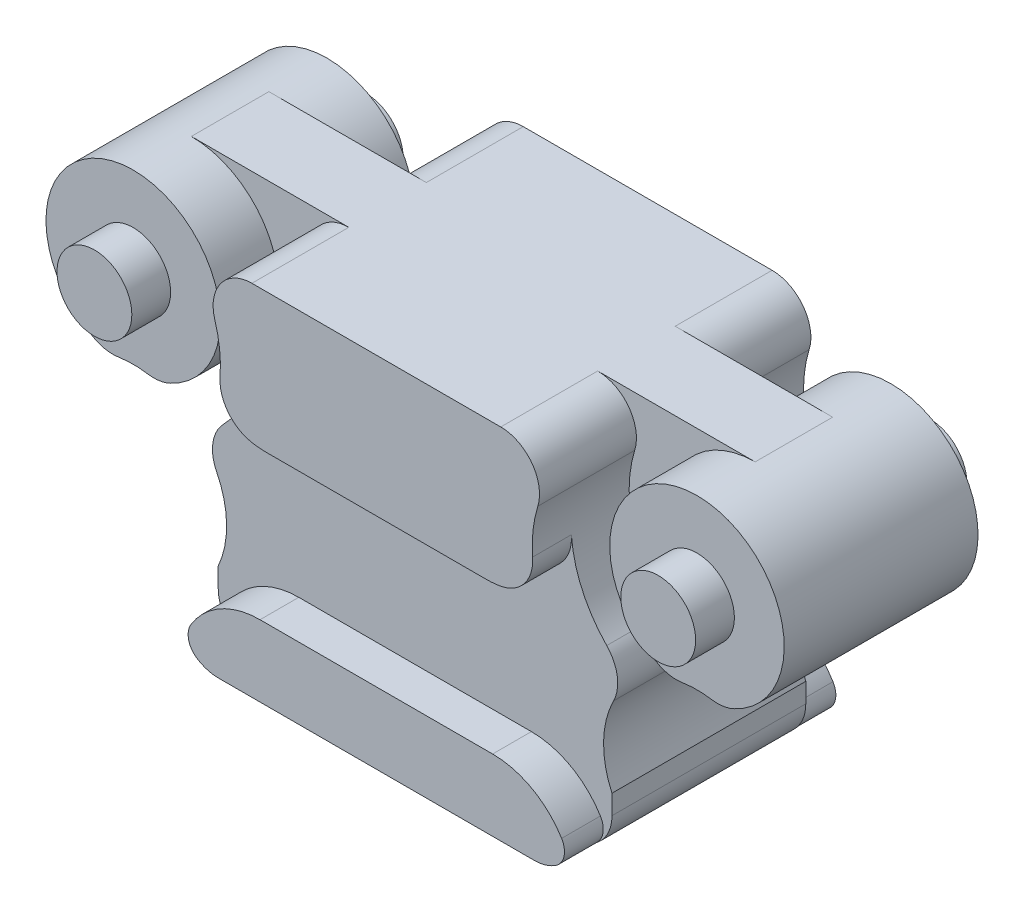
SolidWorks part; units mm, degrees
material "ABS"
ref_plane "Front Plane" through (0, 0, 0) normal (0, 0, 1) x (1, 0, 0)
ref_plane "Top Plane" through (0, 0, 0) normal (0, 1, 0) x (1, 0, 0)
ref_plane "Right Plane" through (0, 0, 0) normal (1, 0, 0) x (0, 0, -1)
sketch "Sketch1" plane through (0, 0, 0) normal (0, 0, 1) x (1, 0, 0)
  line L0 (5.5562, 0) -> (35.7188, 0)
  line L1 (0, 5.5562) -> (41.275, 5.5562)
  line L2 (0, 5.5562) -> (0, -5.5562) construction
  line L3 (0, -5.5562) -> (41.275, -5.5562) construction
  line L4 (41.275, 5.5562) -> (41.275, -5.5562) construction
  line L5 (0, 5.5562) -> (41.275, 5.5562) construction
  line L9 (0, 0) -> (9.0934, 0.7956) construction
  line L10 (41.275, 9.1281) -> (41.275, 0) construction
  line L11 (32.1816, 0.7956) -> (30.4025, 0.9512) construction
  line L12 (32.1816, 0.7956) -> (41.275, 0) construction
  line L13 (30.4025, 0.9512) -> (28.6233, 1.1069) construction
  circle A0 centre (0, 0) radius 5.5562 construction
  circle A1 centre (41.275, 0) radius 5.5562 construction
  arc A2 (0, 5.5562) -> (0, -5.5562) centre (0, 0) ccw
  arc A3 (41.275, -5.5562) -> (41.275, 5.5562) centre (41.275, 0) ccw
  circle A4 centre (0, 0) radius 1.7859
  circle A5 centre (41.275, 0) radius 1.7859
  arc A6 (0, -5.5562) -> (5.5562, 0) centre (0, 0) ccw
  arc A7 (35.7188, 0) -> (41.275, -5.5562) centre (41.275, 0) ccw
  circle A16 centre (41.275, -9.1281) radius 1.7859
  circle A20 centre (41.275, -9.1281) radius 3.5719
  circle A21 centre (32.1816, 0.7956) radius 1.7859
  circle A22 centre (32.1816, 0.7956) radius 3.5719 construction
  circle A23 centre (41.275, 0) radius 9.1281 construction
  circle A25 centre (0, 0) radius 9.1281 construction
  circle A40 centre (32.1816, 7.9393) radius 1.7859
  circle A41 centre (32.1816, 7.9393) radius 3.5719
  circle A42 centre (0, -9.1281) radius 3.5719
  circle A46 centre (9.0934, 0.7956) radius 1.7859
  circle A47 centre (9.0934, 7.9393) radius 1.7859
  circle A48 centre (9.0934, 7.9393) radius 3.5719
  circle A49 centre (9.0934, 0.7956) radius 3.5719 construction
  circle A50 centre (0, -9.1281) radius 1.7859
  arc A51 (0, -7.3422) -> (7.3142, 0.6399) centre (0, 0) ccw
  arc A52 (0, -10.9141) -> (10.8725, 0.9512) centre (0, 0) ccw
  arc A53 (0, -12.7) -> (12.6517, 1.1069) centre (0, 0) ccw
  arc A54 (28.6233, 1.1069) -> (41.275, -12.7) centre (41.275, 0) ccw
  arc A55 (30.4025, 0.9512) -> (41.275, -10.9141) centre (41.275, 0) ccw
  arc A56 (33.9608, 0.6399) -> (41.275, -7.3422) centre (41.275, 0) ccw
  dimension "D1" = 41.275
  dimension "D2" = 11.1125
  dimension "D3" = 3.5719
  dimension "D5" = 95
  dimension "D6" = 7.1438
  dimension "D7" = 3.5719
  dimension "D4" = 95
sketch "Sketch2" plane through (0, 0, 0) normal (0, 0, 1) x (1, 0, 0)
  line L0 (9.0934, 11.5112) -> (32.1816, 11.5112)
  line L1 (12.5755, 0) -> (28.6995, 0)
  line L2 (5.5562, 0) -> (35.7188, 0) construction
  line L3 (12.5755, 0) -> (12.5755, -3.175)
  line L4 (12.5755, -3.175) -> (28.6995, -3.175)
  line L5 (28.6995, -3.175) -> (28.6995, 0)
  circle A0 centre (32.1816, 0.7956) radius 3.5719
  circle A1 centre (9.0934, 0.7956) radius 3.5719
  circle A2 centre (9.0934, 7.9393) radius 3.5719
  circle A3 centre (32.1816, 7.9393) radius 3.5719
  circle A4 centre (9.0934, 7.9393) radius 3.5719 construction
  circle A5 centre (32.1816, 0.7956) radius 3.5719 construction
  circle A6 centre (9.0934, 0.7956) radius 3.5719 construction
  circle A7 centre (9.0934, 7.9393) radius 1.5319
  circle A8 centre (32.1816, 7.9393) radius 1.5319
  circle A9 centre (9.0934, 0.7956) radius 3.8259
  circle A10 centre (32.1816, 0.7956) radius 3.8259
  dimension "D2" = 3.0639
  dimension "D3" = 0.254
  dimension "D1" = 3.175
extrude "Boss-Extrude1" add sketch "Sketch2" along normal blind 7.9375 contours A3 L0 A2 A1 L1 A0 | A2 A7 | A3 A8 | L4 L5 L1 L3 region at (20.6375, 5.8629, 0) region at (11.5483, 10.3942, 0) region at (34.6365, 10.3942, 0) region at (20.6375, -1.5934, 0)
extrude "Boss-Extrude2" add sketch "Sketch2<3>" along normal blind 9.525 and the other way blind 1.5875 contours A7 | A8 region at (9.0934, 7.9393, 0)
sketch "Sketch2<3>" plane through (0, 0, 0) normal (0, 0, 1) x (1, 0, 0) same geometry as "Sketch2"
fillet "Fillet1" radius 1.5875 2 edges at (28.6995, -3.175, 3.9688) (12.5755, -3.175, 3.9688)
sketch "Sketch3" plane through (0, -3.175, 0) normal (0, -1, 0) x (-1, 0, 0)
  line L0 (-14.163, -3.9688) -> (-27.112, -3.9688) construction
  line L1 (-14.163, -7.9375) -> (-27.112, -7.9375) construction
  line L2 (-14.163, -7.9375) -> (-14.163, 0) construction
  line L3 (-14.163, 0) -> (-27.112, 0) construction
  line L4 (-27.112, -7.9375) -> (-27.112, 0) construction
  line L6 (-15.7505, -1.5875) -> (-17.338, -1.5875)
  line L7 (-15.7505, -1.5875) -> (-15.7505, -6.35)
  line L8 (-15.7505, -6.35) -> (-17.338, -6.35)
  line L9 (-17.338, -1.5875) -> (-17.338, -6.35)
  line L10 (-15.7505, -1.5875) -> (-17.338, -6.35) construction
  line L11 (-15.7505, -6.35) -> (-17.338, -1.5875) construction
  line L12 (-19.8437, -1.5875) -> (-21.4312, -1.5875)
  line L13 (-19.8437, -1.5875) -> (-19.8437, -6.35)
  line L14 (-19.8437, -6.35) -> (-21.4312, -6.35)
  line L15 (-21.4312, -1.5875) -> (-21.4312, -6.35)
  line L16 (-19.8437, -1.5875) -> (-21.4312, -6.35) construction
  line L17 (-19.8437, -6.35) -> (-21.4312, -1.5875) construction
  line L18 (-23.937, -1.5875) -> (-25.5245, -1.5875)
  line L19 (-23.937, -1.5875) -> (-23.937, -6.35)
  line L20 (-23.937, -6.35) -> (-25.5245, -6.35)
  line L21 (-25.5245, -1.5875) -> (-25.5245, -6.35)
  line L22 (-23.937, -1.5875) -> (-25.5245, -6.35) construction
  line L23 (-23.937, -6.35) -> (-25.5245, -1.5875) construction
  point P8 (-16.5443, -3.9688)
  point P13 (-20.6375, -3.9688)
  point P18 (-24.7307, -3.9688)
  dimension "D1" = 1.5875
  dimension "D2" = 1.5875
  dimension "D3" = 1.5875
  dimension "D4" = 4.7625
extrude "Cut-Extrude1" cut sketch "Sketch3" against normal blind 3.175
sketch "Sketch5" plane through (0, 0, 7.9375) normal (0, 0, 1) x (1, 0, 0)
  line L0 (5.5216, 7.9125) -> (35.7534, 7.9125) construction
  line L1 (9.0934, 11.5112) -> (32.1816, 11.5112) construction
  line L2 (5.5216, 7.9125) -> (11.7547, 11.5112) construction
  arc A0 (9.0934, 11.5112) -> (8.1331, 4.499) centre (9.0934, 7.9393) ccw construction
  arc A1 (33.1419, 4.499) -> (32.1816, 11.5112) centre (32.1816, 7.9393) ccw construction
  dimension "D1" = 3.5987
  dimension "D2" = 30
sketch3d "3DSketch1"
  line L2 (9.0934, 11.5112, 0) -> (32.1816, 11.5112, 0) construction
  line L3 (11.7547, 11.5112, 7.9375) -> (11.7547, 11.5112, 0) construction
sketch3d "3DSketch4"
  line L0 (11.7547, 11.5112, 7.9375) -> (11.7547, 11.5112, 0) construction
  line L1 (5.5216, 7.9125, 7.9375) -> (11.7547, 11.5112, 7.9375) construction
sketch3d "3DSketch6"
sketch "Sketch7" plane through (-2.0458, 3.5435, 0) normal (0.5, -0.866, 0) x (-0.866, -0.5, 0)
  line L0 (-8.7381, -7.9375) -> (-8.7381, 0) construction
  line L1 (-8.2729, 0) -> (-13.6307, 0) construction
ref_plane "Plane2" through (35.7535, 0, 0) normal (1, 0, 0) x (0, 0, -1)
sketch "Sketch8" plane through (7.5674, 4.3691, 0) normal (0.866, 0.5, 0) x (0, 0, -1)
  line L0 (-7.9375, 4.0916) -> (0, 4.0916) construction
  line L2 (-4.7816, 3.2788) -> (-3.156, 3.2788)
  line L3 (-4.7816, 3.2788) -> (-4.7816, 4.9044)
  line L4 (-4.7816, 4.9044) -> (-3.156, 4.9044)
  line L5 (-3.156, 3.2788) -> (-3.156, 4.9044)
  line L6 (-4.7816, 3.2788) -> (-3.156, 4.9044) construction
  line L7 (-4.7816, 4.9044) -> (-3.156, 3.2788) construction
  circle A0 centre (-3.9688, 4.0916) radius 0.8128 construction
  point P4 (-3.9688, 4.0916)
  dimension "D1" = 1.6256
extrude "Cut-Extrude2" [suppressed] cut sketch "Sketch8" against normal through all both and the other way through all
sketch "Sketch9" plane through (35.7535, 0, 0) normal (1, 0, 0) x (0, 0, -1)
  line L0 (-7.9375, 7.9393) -> (0, 7.9393) construction
  line L1 (-7.9375, 9.4713) -> (-7.9375, 6.4074) construction
  line L2 (0, 6.4074) -> (0, 9.4713) construction
  line L4 (-4.3751, 7.5329) -> (-3.5624, 7.5329)
  line L5 (-4.3751, 7.5329) -> (-4.3751, 8.3457)
  line L6 (-4.3751, 8.3457) -> (-3.5624, 8.3457)
  line L7 (-3.5624, 7.5329) -> (-3.5624, 8.3457)
  line L8 (-4.3751, 7.5329) -> (-3.5624, 8.3457) construction
  line L9 (-4.3751, 8.3457) -> (-3.5624, 7.5329) construction
  circle A0 centre (-3.9688, 7.9393) radius 0.4064 construction
  dimension "D1" = 0.8128
extrude "Cut-Extrude3" [suppressed] cut sketch "Sketch9" against normal blind 0.8928
sketch "Sketch10" plane through (0, 0, 7.9375) normal (0, 0, 1) x (1, 0, 0)
  line L0 (9.0934, 11.5112) -> (12.8164, 11.5112)
  line L1 (9.0934, 11.5112) -> (32.1816, 11.5112) construction
  line L2 (32.1816, 11.5112) -> (28.4586, 11.5112)
  circle A0 centre (9.0934, 7.9393) radius 3.5719
  circle A1 centre (9.0934, 7.9393) radius 5.1594
  circle A2 centre (32.1816, 7.9393) radius 3.5719
  circle A3 centre (32.1816, 7.9393) radius 5.1594
  arc A4 (33.1419, 4.499) -> (32.1816, 11.5112) centre (32.1816, 7.9393) ccw construction
  arc A5 (33.1419, 4.499) -> (28.6995, -0.7893) centre (32.1816, 0.7956) ccw construction
  arc A7 (32.1816, 4.3674) -> (29.7343, 3.3973) centre (32.1816, 0.7956) ccw
  arc A8 (11.5407, 3.3973) -> (9.0934, 4.3674) centre (9.0934, 0.7956) ccw
  circle A9 centre (32.1816, 7.9393) radius 1.5319 construction
  arc A10 (12.5755, -0.7893) -> (8.1331, 4.499) centre (9.0934, 0.7956) ccw construction
  line M9 (32.1816, 11.5112) -> (9.0934, 11.5112)
  dimension "D1" = 1.5875
  dimension "D2" = 1.5875
  dimension "D3" = 0.254
  dimension "D4" = 0.254
extrude "Cut-Extrude4" cut sketch "Sketch10" against normal blind 2.3812 contours A1 A0 M9 | A3 A2 M9 region at (10.9549, 11.415, 7.9375) region at (30.3201, 11.415, 7.9375)
extrude "Cut-Extrude5" cut sketch "Sketch10<3>" against normal blind 2.3812 from offset 5.5562 contours A1 A0 M9 | A3 A2 M9 region at (10.9549, 11.415, 7.9375) region at (30.3201, 11.415, 7.9375) offset against normal yes
sketch "Sketch10<3>" plane through (0, 0, 7.9375) normal (0, 0, 1) x (1, 0, 0) same geometry as "Sketch10"
fillet "Fillet2" radius 1.5875 8 edges at (28.4586, 11.5112, 1.1906) (28.4586, 11.5112, 6.7469) (12.8164, 11.5112, 6.7469) (12.8164, 11.5112, 1.1906) (11.7705, 3.5288, 1.1906) (29.5045, 3.5288, 1.1906) (29.5045, 3.5288, 6.7469) (11.7705, 3.5288, 6.7469)
fillet "Fillet4" [suppressed] radius 1.5875
fillet "Fillet5" [suppressed] radius 0.1985
sketch "Sketch11" plane through (0, 0, 7.9375) normal (0, 0, 1) x (1, 0, 0)
  line L0 (27.6056, 5.5563) -> (13.6694, 5.5562)
  line L3 (0, 5.5562) -> (41.275, 5.5562) construction
  line L4 (25.7332, 11.5112) -> (15.5418, 11.5112)
  line L5 (12.5755, -0.7893) -> (12.5755, -1.5875)
  line L6 (14.163, -3.175) -> (27.112, -3.175)
  line L7 (28.6995, -1.5875) -> (28.6995, -0.7893)
  line L8 (25.7332, 11.5112) -> (15.5418, 11.5112)
  line L9 (12.5755, -0.7893) -> (12.5755, -1.5875)
  line L10 (14.163, -3.175) -> (27.112, -3.175)
  line L11 (28.6995, -1.5875) -> (28.6995, -0.7893)
  line L12 (12.8356, 0) -> (28.4394, 0)
  line L13 (5.5562, 0) -> (35.7188, 0) construction
  arc A1 (12.7899, 4.34) -> (14.0246, 9.4568) centre (9.0934, 7.9393) ccw construction
  arc A10 (27.2504, 9.4568) -> (28.4851, 4.34) centre (32.1816, 7.9393) ccw
  arc A11 (27.2504, 9.4568) -> (25.7332, 11.5112) centre (25.7332, 9.9237) ccw
  arc A12 (15.5418, 11.5112) -> (14.0246, 9.4568) centre (15.5418, 9.9237) ccw
  arc A13 (12.7899, 4.34) -> (14.0246, 9.4568) centre (9.0934, 7.9393) ccw
  arc A14 (12.5755, -0.7893) -> (12.5097, 2.5178) centre (9.0934, 0.7956) ccw
  arc A15 (12.5755, -0.7893) -> (12.5097, 2.5178) centre (9.0934, 0.7956) ccw
  arc A16 (12.5755, -1.5875) -> (14.163, -3.175) centre (14.163, -1.5875) ccw
  arc A17 (27.112, -3.175) -> (28.6995, -1.5875) centre (27.112, -1.5875) ccw
  arc A18 (28.7653, 2.5178) -> (28.6995, -0.7893) centre (32.1816, 0.7956) ccw
  arc A19 (28.7653, 2.5178) -> (28.6995, -0.7893) centre (32.1816, 0.7956) ccw
  arc A20 (27.2504, 9.4568) -> (28.4851, 4.34) centre (32.1816, 7.9393) ccw
  arc A21 (27.2504, 9.4568) -> (25.7332, 11.5112) centre (25.7332, 9.9237) ccw
  arc A22 (15.5418, 11.5112) -> (14.0246, 9.4568) centre (15.5418, 9.9237) ccw
  arc A23 (12.7899, 4.34) -> (14.0246, 9.4568) centre (9.0934, 7.9393) ccw
  arc A26 (12.5755, -1.5875) -> (14.163, -3.175) centre (14.163, -1.5875) ccw
  arc A27 (27.112, -3.175) -> (28.6995, -1.5875) centre (27.112, -1.5875) ccw
  arc A32 (28.7653, 2.5178) -> (28.4851, 4.34) centre (27.3478, 3.2325) ccw
  arc A33 (28.7653, 2.5178) -> (28.4851, 4.34) centre (27.3478, 3.2325) ccw
  arc A34 (12.7899, 4.34) -> (12.5097, 2.5178) centre (13.9272, 3.2325) ccw
  arc A35 (12.7899, 4.34) -> (12.5097, 2.5178) centre (13.9272, 3.2325) ccw
  arc M16 (28.4851, 4.34) -> (27.2504, 9.4568) centre (32.1816, 7.9393) cw
  arc M17 (27.2504, 9.4568) -> (25.7332, 11.5112) centre (25.7332, 9.9237) ccw
  line M18 (25.7332, 11.5112) -> (15.5418, 11.5112)
  arc M19 (15.5418, 11.5112) -> (14.0246, 9.4568) centre (15.5418, 9.9237) ccw
  arc M20 (14.0246, 9.4568) -> (12.7899, 4.34) centre (9.0934, 7.9393) cw
  line M23 (12.5755, -0.7893) -> (12.5755, -1.5875)
  arc M24 (12.5755, -1.5875) -> (14.163, -3.175) centre (14.163, -1.5875) ccw
  line M25 (14.163, -3.175) -> (27.112, -3.175)
  arc M26 (27.112, -3.175) -> (28.6995, -1.5875) centre (27.112, -1.5875) ccw
  line M27 (28.6995, -1.5875) -> (28.6995, -0.7893)
  dimension "D1" = 0
extrude "Boss-Extrude3" add sketch "Sketch11" along normal blind 1.5875 contours L0 M16 M17 M18 M19 M20 | M23 M24 M25 M26 M27 region at (20.6375, 8.5013, 7.9375) region at (20.6375, -1.5668, 7.9375)
extrude "Boss-Extrude4" add sketch "Sketch11<3>" against normal blind 1.5875 from surface contours L0 M16 M17 M18 M19 M20 | M23 M24 M25 M26 M27 region at (20.6375, 8.5013, 7.9375) region at (20.6375, -1.5668, 7.9375) starting at face at (10.6253, 7.9393, 0)
sketch "Sketch11<3>" plane through (0, 0, 7.9375) normal (0, 0, 1) x (1, 0, 0) same geometry as "Sketch11"
sketch "Sketch14" plane through (0, 0, 9.525) normal (0, 0, 1) x (1, 0, 0)
  line L0 (19.4469, -3.5719) -> (21.8281, -3.5719) construction
  line L1 (19.7079, 9.1281) -> (21.5671, 9.1281) construction
  line L2 (13.6694, 5.5562) -> (27.6056, 5.5563)
  line L3 (25.7332, 11.5112) -> (15.5418, 11.5112)
  line L4 (13.6694, 5.5562) -> (27.6056, 5.5563)
  line L5 (25.7332, 11.5112) -> (15.5418, 11.5112)
  line L6 (20.6375, 9.1281) -> (20.6375, -3.5719) construction
  line L7 (27.6056, 5.5563) -> (13.6694, 5.5562) construction
  line L8 (28.4394, 0) -> (12.8356, 0)
  line L9 (12.5755, -0.7893) -> (12.5755, -1.5875)
  line L10 (14.163, -3.175) -> (27.112, -3.175)
  line L11 (28.6995, -1.5875) -> (28.6995, -0.7893)
  line L12 (28.4394, 0) -> (12.8356, 0)
  line L13 (12.5755, -0.7893) -> (12.5755, -1.5875)
  line L14 (14.163, -3.175) -> (27.112, -3.175)
  line L15 (28.6995, -1.5875) -> (28.6995, -0.7893)
  circle A0 centre (16.136, 9.1281) radius 3.5719
  circle A1 centre (25.139, 9.1281) radius 3.5719
  circle A2 centre (25.4, -3.5719) radius 3.5719
  circle A3 centre (15.875, -3.5719) radius 3.5719
  arc A4 (27.2504, 9.4568) -> (27.6056, 5.5563) centre (32.1816, 7.9393) ccw
  arc A5 (27.2504, 9.4568) -> (25.7332, 11.5112) centre (25.7332, 9.9237) ccw
  arc A6 (15.5418, 11.5112) -> (14.0246, 9.4568) centre (15.5418, 9.9237) ccw
  arc A7 (13.6694, 5.5562) -> (14.0246, 9.4568) centre (9.0934, 7.9393) ccw
  arc A8 (27.2504, 9.4568) -> (27.6056, 5.5563) centre (32.1816, 7.9393) ccw
  arc A9 (27.2504, 9.4568) -> (25.7332, 11.5112) centre (25.7332, 9.9237) ccw
  arc A10 (15.5418, 11.5112) -> (14.0246, 9.4568) centre (15.5418, 9.9237) ccw
  arc A11 (13.6694, 5.5562) -> (14.0246, 9.4568) centre (9.0934, 7.9393) ccw
  arc A12 (12.5755, -0.7893) -> (12.8356, 0) centre (9.0934, 0.7956) ccw
  arc A13 (12.5755, -1.5875) -> (14.163, -3.175) centre (14.163, -1.5875) ccw
  arc A14 (27.112, -3.175) -> (28.6995, -1.5875) centre (27.112, -1.5875) ccw
  arc A15 (28.4394, 0) -> (28.6995, -0.7893) centre (32.1816, 0.7956) ccw
  arc A16 (12.5755, -0.7893) -> (12.8356, 0) centre (9.0934, 0.7956) ccw
  arc A17 (12.5755, -1.5875) -> (14.163, -3.175) centre (14.163, -1.5875) ccw
  arc A18 (27.112, -3.175) -> (28.6995, -1.5875) centre (27.112, -1.5875) ccw
  arc A19 (28.4394, 0) -> (28.6995, -0.7893) centre (32.1816, 0.7956) ccw
  point P30 (16.136, 5.5562)
  point P31 (25.139, 5.5563)
  point P32 (25.4, 0)
  point P33 (15.875, 0)
  point P38 (20.6375, 5.5562)
  line M20 (13.6694, 5.5562) -> (27.6056, 5.5563)
  arc M21 (27.6056, 5.5563) -> (27.2504, 9.4568) centre (32.1816, 7.9393) cw
  arc M25 (14.0246, 9.4568) -> (13.6694, 5.5562) centre (9.0934, 7.9393) cw
  dimension "D4" = 7.1437
  dimension "D3" = 9.525
  dimension "D5" = 9.003
  dimension "D1" = 0
  dimension "D2" = 0
extrude "Cut-Extrude10" cut sketch "Sketch14" against normal blind 1.5875 contours L13 A17 A3 L12 A16 | A19 L12 A2 A18 L15 | A1 M20 M21 | A0 M25 M20 region at (14.3981, 5.7727, 9.525) region at (26.8769, 5.7727, 9.525) region at (27.8861, -0.6097, 9.525) region at (13.3889, -0.6097, 9.525)
extrude "Cut-Extrude11" cut sketch "Sketch14<3>" against normal blind 1.5875 from surface contours L13 A17 A3 L12 A16 | A19 L12 A2 A18 L15 | A1 M20 M21 | A0 M25 M20 region at (14.3981, 5.7727, 9.525) region at (26.8769, 5.7727, 9.525) region at (27.8861, -0.6097, 9.525) region at (13.3889, -0.6097, 9.525) starting at face at (10.6253, 7.9393, 0)
sketch "Sketch14<3>" plane through (0, 0, 9.525) normal (0, 0, 1) x (1, 0, 0) same geometry as "Sketch14"
sketch "Sketch15" plane through (0, 0, 9.525) normal (0, 0, 1) x (1, 0, 0)
  line L0 (25.7332, 11.2572) -> (15.5418, 11.2572)
  line L1 (16.136, 5.8102) -> (25.139, 5.8103)
  line L2 (16.136, 5.5562) -> (25.139, 5.5563)
  line L3 (25.7332, 11.5112) -> (15.5418, 11.5112)
  line L4 (16.136, 5.5562) -> (25.139, 5.5563)
  line L5 (25.7332, 11.5112) -> (15.5418, 11.5112)
  line L6 (25.4, 0) -> (15.875, 0)
  line L7 (14.163, -3.175) -> (27.112, -3.175)
  line L8 (25.4, 0) -> (15.875, 0)
  line L9 (14.163, -3.175) -> (27.112, -3.175)
  line L10 (25.4, -0.254) -> (15.875, -0.254)
  line L11 (14.163, -2.921) -> (27.112, -2.921)
  arc A0 (14.2773, 6.3798) -> (14.2673, 9.5315) centre (9.0934, 7.9393) ccw
  arc A1 (15.5418, 11.2572) -> (14.2673, 9.5315) centre (15.5418, 9.9237) ccw
  arc A2 (27.0077, 9.5315) -> (25.7332, 11.2572) centre (25.7332, 9.9237) ccw
  arc A3 (27.0077, 9.5315) -> (26.9977, 6.3798) centre (32.1816, 7.9393) ccw
  arc A4 (27.112, -3.175) -> (28.6309, -2.0489) centre (27.112, -1.5875) ccw
  arc A5 (28.6309, -2.0489) -> (25.4, 0) centre (25.4, -3.5719) ccw
  arc A6 (13.979, 6.2811) -> (14.0246, 9.4568) centre (9.0934, 7.9393) ccw
  arc A7 (13.979, 6.2811) -> (16.136, 5.5562) centre (16.136, 9.1281) ccw
  arc A8 (25.139, 5.5563) -> (27.296, 6.2811) centre (25.139, 9.1281) ccw
  arc A9 (27.2504, 9.4568) -> (27.296, 6.2811) centre (32.1816, 7.9393) ccw
  arc A10 (27.2504, 9.4568) -> (25.7332, 11.5112) centre (25.7332, 9.9237) ccw
  arc A11 (15.5418, 11.5112) -> (14.0246, 9.4568) centre (15.5418, 9.9237) ccw
  arc A12 (13.979, 6.2811) -> (14.0246, 9.4568) centre (9.0934, 7.9393) ccw
  arc A13 (13.979, 6.2811) -> (16.136, 5.5562) centre (16.136, 9.1281) ccw
  arc A14 (25.139, 5.5563) -> (27.296, 6.2811) centre (25.139, 9.1281) ccw
  arc A15 (27.2504, 9.4568) -> (27.296, 6.2811) centre (32.1816, 7.9393) ccw
  arc A16 (27.2504, 9.4568) -> (25.7332, 11.5112) centre (25.7332, 9.9237) ccw
  arc A17 (15.5418, 11.5112) -> (14.0246, 9.4568) centre (15.5418, 9.9237) ccw
  arc A18 (15.875, 0) -> (12.6441, -2.0489) centre (15.875, -3.5719) ccw
  arc A19 (12.6441, -2.0489) -> (14.163, -3.175) centre (14.163, -1.5875) ccw
  arc A20 (27.112, -3.175) -> (28.6309, -2.0489) centre (27.112, -1.5875) ccw
  arc A21 (28.6309, -2.0489) -> (25.4, 0) centre (25.4, -3.5719) ccw
  arc A22 (15.875, 0) -> (12.6441, -2.0489) centre (15.875, -3.5719) ccw
  arc A23 (12.6441, -2.0489) -> (14.163, -3.175) centre (14.163, -1.5875) ccw
  arc A24 (25.139, 5.8103) -> (27.2155, 6.5404) centre (25.139, 9.1281) ccw
  arc A25 (14.0595, 6.5404) -> (16.136, 5.8102) centre (16.136, 9.1281) ccw
  arc A26 (27.112, -2.921) -> (28.3566, -2.0662) centre (27.112, -1.5875) ccw
  arc A27 (28.4928, -2.3707) -> (25.4, -0.254) centre (25.4, -3.5719) ccw
  arc A28 (15.875, -0.254) -> (12.7822, -2.3707) centre (15.875, -3.5719) ccw
  arc A29 (12.9184, -2.0662) -> (14.163, -2.921) centre (14.163, -1.5875) ccw
  arc A30 (14.2773, 6.3798) -> (16.136, 5.8102) centre (16.136, 9.1281) ccw construction
  arc A31 (25.139, 5.8103) -> (26.9977, 6.3798) centre (25.139, 9.1281) ccw construction
  arc A32 (28.3566, -2.0662) -> (25.4, -0.254) centre (25.4, -3.5719) ccw construction
  arc A33 (15.875, -0.254) -> (12.9184, -2.0662) centre (15.875, -3.5719) ccw construction
  arc M30 (13.979, 6.2811) -> (16.136, 5.5562) centre (16.136, 9.1281) ccw
  line M31 (16.136, 5.5562) -> (25.139, 5.5562)
  arc M32 (25.139, 5.5562) -> (27.296, 6.2811) centre (25.139, 9.1281) ccw
  arc M33 (27.296, 6.2811) -> (27.2504, 9.4568) centre (32.1816, 7.9393) cw
  dimension "D1" = 0
  dimension "D2" = 0
  dimension "D3" = 0.254
  dimension "D4" = 0.254
extrude "Cut-Extrude12" cut sketch "Sketch15" against normal blind 1.5875 contours A25 A12 A24 L1 M30 M31 M32 M33 | A28 L10 A27 A20 A21 L8 A22 A23 region at (20.6375, 5.7656, 9.525) region at (27.2264, -0.6919, 9.525)
extrude "Cut-Extrude13" cut sketch "Sketch15<3>" against normal blind 1.5875 from surface contours A25 A12 A24 L1 M30 M31 M32 M33 | A28 L10 A27 A20 A21 L8 A22 A23 region at (20.6375, 5.7656, 9.525) region at (27.2264, -0.6919, 9.525) starting at face at (10.6253, 7.9393, 0)
sketch "Sketch15<3>" plane through (0, 0, 9.525) normal (0, 0, 1) x (1, 0, 0) same geometry as "Sketch15"
fillet "Fillet11" radius 0.7937 4 edges at (28.4928, -2.3707, -0.7937) (28.4928, -2.3707, 8.7312) (12.7822, -2.3707, -0.7937) (12.7822, -2.3707, 8.7312)
fillet "Fillet12" radius 1.5875 4 edges at (27.2155, 6.5404, 8.7312) (27.2155, 6.5404, -0.7937) (14.0595, 6.5404, -0.7937) (14.0595, 6.5404, 8.7312)
fillet "Fillet13" radius 1.5875 6 edges at (31.2213, 4.499, 1.1906) (33.1419, 4.499, 3.9688) (31.2213, 4.499, 6.7469) (10.0537, 4.499, 1.1906) (10.0537, 4.499, 6.7469) (8.1331, 4.499, 3.9688)
